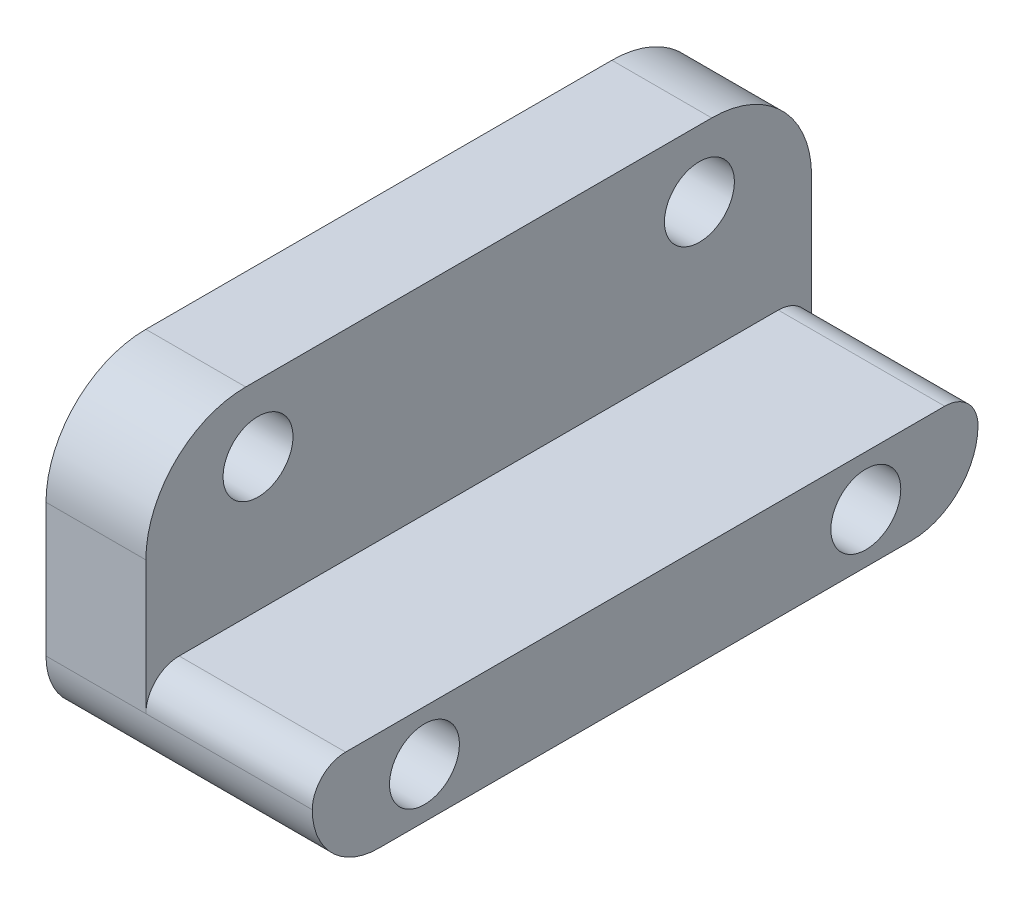
SolidWorks part; units mm, degrees
ref_plane "前视基准面" through (0, 0, 0) normal (0, 0, 1) x (1, 0, 0)
ref_plane "上视基准面" through (0, 0, 0) normal (0, 1, 0) x (1, 0, 0)
ref_plane "右视基准面" through (0, 0, 0) normal (1, 0, 0) x (0, 0, -1)
other "Configuration Table"
sketch "草图1" plane through (0, 0, 0) normal (1, 0, 0) x (0, 0, -1)
  line L0 (10, -9) -> (10, 0) construction
  line L1 (0, 0) -> (20, 0)
  line L2 (0, 0) -> (0, -9)
  line L3 (0, -9) -> (20, -9)
  line L4 (20, 0) -> (20, -9)
  circle A0 centre (3.37, -2) radius 1.05
  circle A1 centre (16.63, -2) radius 1.05
  dimension "D3" = 2.1
  dimension "D1" = 20
  dimension "D2" = 9
  dimension "D4" = 6.63
  dimension "D5" = 2
extrude "凸台-拉伸1" add sketch "草图1" along normal blind 3
sketch "草图2" plane through (3, 0, 0) normal (1, 0, 0) x (0, 0, -1)
  line L0 (20, -9) -> (20, 0) construction
  line L1 (0, -9) -> (20, -9)
  line L2 (0, -9) -> (0, -6)
  line L3 (0, -6) -> (20, -6)
  line L4 (20, -9) -> (20, -6)
  dimension "D1" = 3
extrude "凸台-拉伸2" add sketch "草图2" along normal blind 5
sketch "草图3" plane through (8, 0, 0) normal (1, 0, 0) x (0, 0, -1)
  line L0 (10, -6) -> (10, -9) construction
  line L1 (20, -6) -> (0, -6) construction
  line L2 (0, -9) -> (20, -9) construction
  circle A0 centre (3.37, -7.5) radius 1.05
  circle A1 centre (16.63, -7.5) radius 1.05
  dimension "D1" = 2.1
  dimension "D2" = 6.63
  dimension "D3" = 1.5
extrude "切除-拉伸1" cut sketch "草图3" against normal blind 10
fillet "圆角1" radius 3 1 edges at (1.5, 0, 0) type face fillet first side face at (1.5, 0, -10) second side face at (3.6667, -5, 0)
fillet "圆角2" radius 3 1 edges at (1.5, 0, -20) type face fillet first side face at (1.5, 0, -11.5) second side face at (3.6667, -5, -20)
fillet "圆角3" radius 2 1 edges at (4, -9, -20) type face fillet first side face at (3.6667, -6, -20) second side face at (4, -9, -10)
fillet "圆角4" radius 2 1 edges at (4, -9, 0) type face fillet first side face at (3.6667, -6, 0) second side face at (4, -9, -9)
fillet "圆角7" radius 1 1 edges at (5.5, -6, 0) type face fillet first side face at (5.5, -6, -10) second side face at (3.6667, -5.3333, 0)
fillet "圆角8" radius 1 1 edges at (5.5, -6, -20) type face fillet first side face at (5.5, -6, -10.5) second side face at (3.6667, -5.3333, -20)
